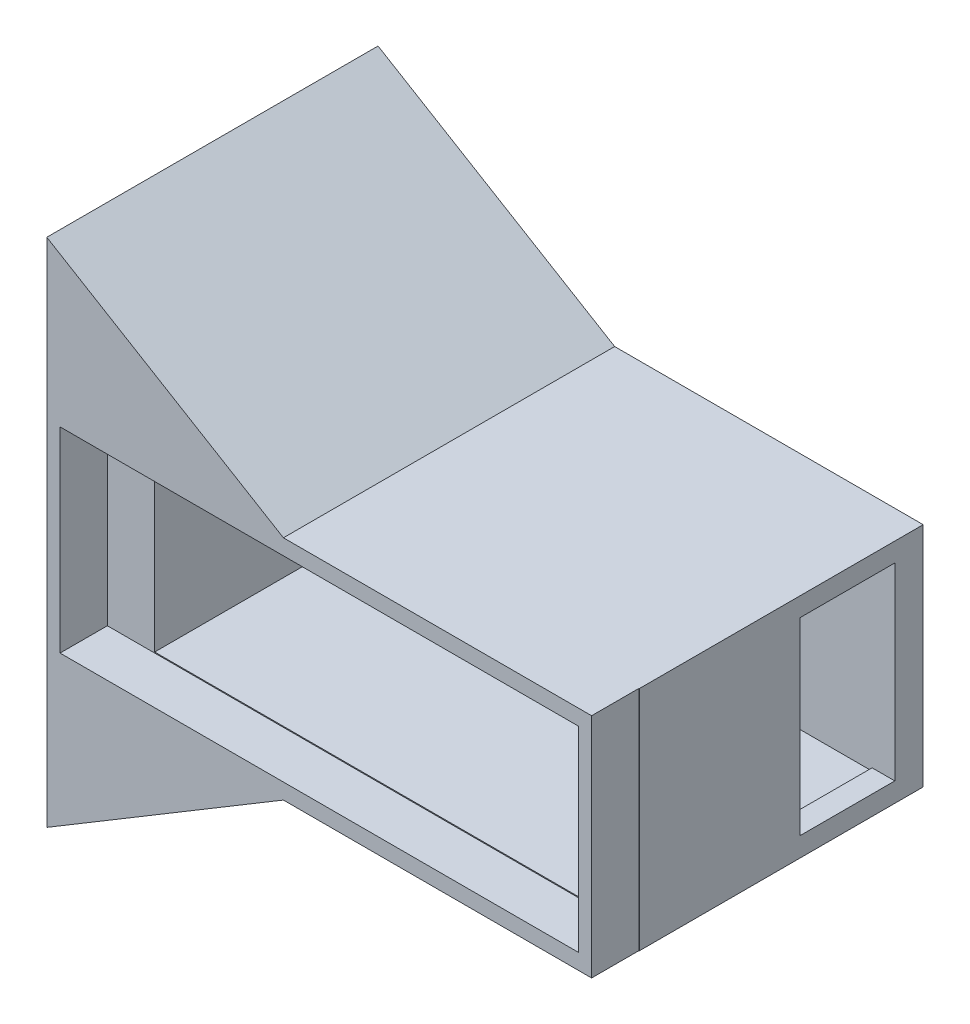
SolidWorks part; units mm, degrees
ref_plane "Front Plane" through (0, 0, 0) normal (0, 0, 1) x (1, 0, 0)
ref_plane "Top Plane" through (0, 0, 0) normal (0, 1, 0) x (1, 0, 0)
ref_plane "Right Plane" through (0, 0, 0) normal (1, 0, 0) x (0, 0, -1)
sketch "Sketch2" plane through (0, 0, 0) normal (0, 0, 1) x (1, 0, 0)
  line L1 (-28.8, 12) -> (28.8, 12)
  line L2 (-28.8, 12) -> (-28.8, -12)
  line L3 (-28.8, -12) -> (28.8, -12)
  line L4 (28.8, 12) -> (28.8, -12)
  line L5 (-28.8, 12) -> (28.8, -12) construction
  line L6 (-28.8, -12) -> (28.8, 12) construction
  point P0 (0, 0)
  dimension "D1" = 24
  dimension "D2" = 57.6
extrude "Boss-Extrude1" add sketch "Sketch2" along normal blind 30
sketch "Sketch5" plane through (0, 0, 30) normal (0, 0, 1) x (1, 0, 0)
  line L1 (-22.4, 10.25) -> (22.4, 10.25)
  line L2 (-22.4, 10.25) -> (-22.4, -10.25)
  line L3 (-22.4, -10.25) -> (22.4, -10.25)
  line L4 (22.4, 10.25) -> (22.4, -10.25)
  line L5 (-22.4, 10.25) -> (22.4, -10.25) construction
  line L6 (-22.4, -10.25) -> (22.4, 10.25) construction
  point P0 (0, 0)
  dimension "D1" = 20.5
  dimension "D2" = 44.8
extrude "Cut-Extrude1" cut sketch "Sketch5" against normal blind 27
sketch "Sketch10" plane through (0, 0, 30) normal (0, 0, 1) x (1, 0, 0)
  line L0 (-28.8, 12) -> (-28.8, -12)
  line L1 (-28.8, 12) -> (28.7632, 12)
  line L2 (-28.8, -12) -> (28.7632, -12)
  line L3 (28.7632, 12) -> (28.7632, -12)
extrude "Boss-Extrude2" add sketch "Sketch10" along normal blind 5
sketch "Sketch11" plane through (0, 0, 35) normal (0, 0, 1) x (1, 0, 0)
  line L1 (-27.4, 10.35) -> (27.4, 10.35)
  line L2 (-27.4, 10.35) -> (-27.4, -10.35)
  line L3 (-27.4, -10.35) -> (27.4, -10.35)
  line L4 (27.4, 10.35) -> (27.4, -10.35)
  line L5 (-27.4, 10.35) -> (27.4, -10.35) construction
  line L6 (-27.4, -10.35) -> (27.4, 10.35) construction
  point P0 (0, 0)
  dimension "D1" = 20.7
  dimension "D2" = 54.8
extrude "Cut-Extrude3" cut sketch "Sketch11" against normal blind 5
sketch "Sketch15" plane through (28.8, 0, 0) normal (1, 0, 0) x (0, 0, -1)
  line L0 (-3, -0.0029) -> (-3, -9.9482)
  line L1 (-3, -0.0029) -> (-3, 9.9971)
  line L2 (-3, 9.9971) -> (-13, 9.9971)
  line L3 (-3, -9.9482) -> (-13, -9.9482)
  line L4 (-13, -9.9482) -> (-13, 9.9971)
extrude "Cut-Extrude4" cut sketch "Sketch15" against normal up to surface (6.4 mm away) up to face at (22.4, 0, 16.5)
sketch "Sketch16" plane through (0, 0, 30) normal (0, 0, 1) x (1, 0, 0)
  line L0 (22.4, -10.25) -> (26.4, -10.25)
  line L3 (22.4, 10.25) -> (22.4, -10.25)
  line L4 (26.4, 10.25) -> (26.4, -10.25)
  line L5 (26.4, 10.25) -> (22.4, 10.25)
extrude "Cut-Extrude5" cut sketch "Sketch16" against normal blind 27 contours L4 L0 L3 L5
sketch "Sketch17" plane through (0, 0, 0) normal (0, 0, 1) x (1, 0, 0)
  line L0 (-28.8, 12) -> (-28.8, 27)
  line L1 (-28.8, 27) -> (-3.8, 12)
  line L2 (28.7632, 12) -> (-28.8, 12) construction
  line L3 (-3.8, 12) -> (-28.8, 12)
  line L4 (-28.8, 0) -> (-15.6964, 0) construction
  line L5 (-28.8, 12) -> (-28.8, -12) construction
  line L10 (-28.8, -27) -> (-3.8, -12)
  line L11 (-28.8, -12) -> (-28.8, -27)
  line L12 (-3.8, -12) -> (-28.8, -12)
extrude "Boss-Extrude3" add sketch "Sketch17" along normal through all
